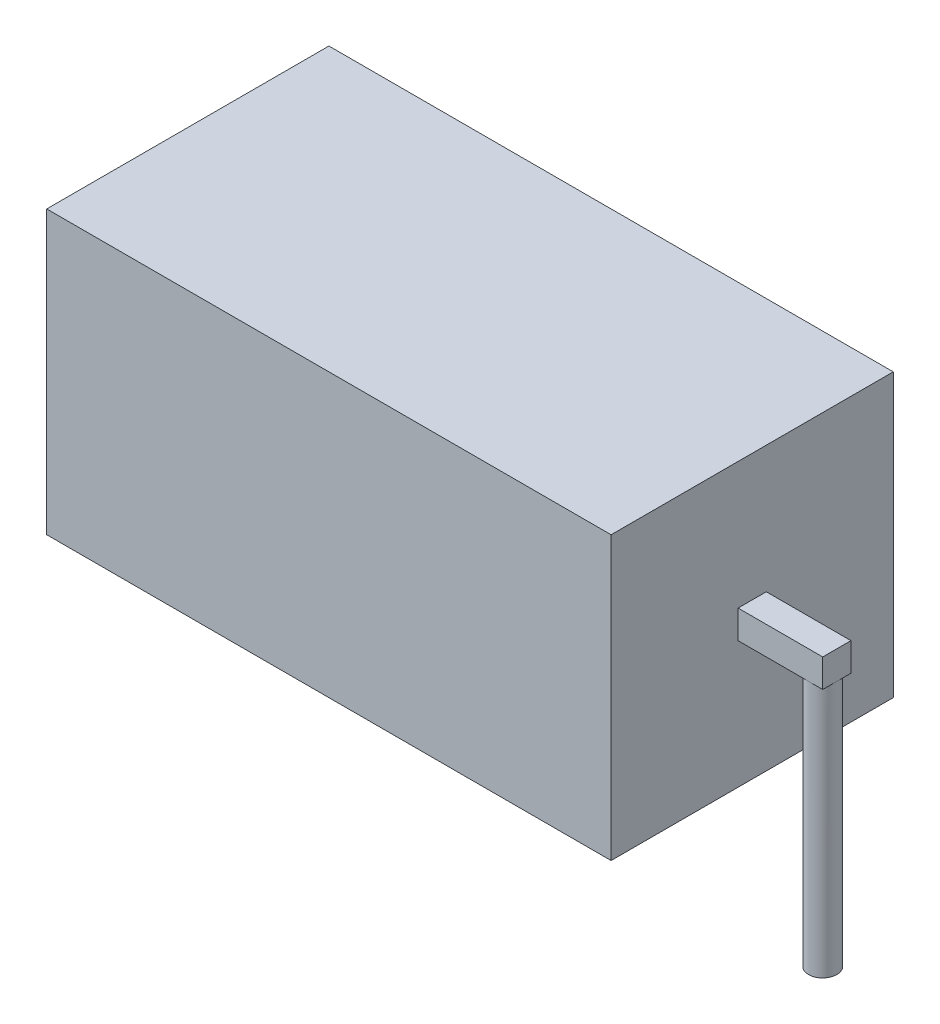
SolidWorks part; units mm, degrees
ref_plane "Спереди" through (0, 0, 0) normal (0, 0, 1) x (1, 0, 0)
ref_plane "Сверху" through (0, 0, 0) normal (0, 1, 0) x (1, 0, 0)
ref_plane "Справа" through (0, 0, 0) normal (1, 0, 0) x (0, 0, -1)
sketch "Эскиз1" plane through (0, 0, 0) normal (0, 0, 1) x (1, 0, 0)
  line L1 (0, 0) -> (20, 0)
  line L2 (0, 0) -> (0, 10)
  line L3 (0, 10) -> (20, 10)
  line L4 (20, 0) -> (20, 10)
  dimension "D1" = 10
  dimension "D2" = 20
extrude "Вытянуть1" add sketch "Эскиз1" along normal blind 10
sketch "Эскиз2" plane through (20, 0, 0) normal (1, 0, 0) x (0, 0, -1)
  line L0 (-10.8705, 5) -> (1.1033, 5) construction
  line L1 (-5, 10.8922) -> (-5, 4.5869) construction
  line L2 (-10, 10) -> (0, 10) construction
  line L3 (-10, 0) -> (0, 0) construction
  line L4 (-10, 0) -> (-10, 10) construction
  line L5 (0, 0) -> (0, 10) construction
  line L7 (-5.5, 4.5) -> (-4.5, 4.5)
  line L8 (-5.5, 4.5) -> (-5.5, 5.5)
  line L9 (-5.5, 5.5) -> (-4.5, 5.5)
  line L10 (-4.5, 4.5) -> (-4.5, 5.5)
  dimension "D1" = 1
extrude "Вытянуть2" add sketch "Эскиз2" along normal blind 3 and the other way blind 23
sketch "Эскиз3" plane through (0, 4.5, 0) normal (0, -1, 0) x (1, 0, 0)
  line L0 (-2.5, 5) -> (23.3087, 5) construction
  line L1 (0, 10) -> (20, 10) construction
  line L2 (0, 0) -> (20, 0) construction
  line L3 (10, 11.1302) -> (10, -1.0428) construction
  line L4 (0, 10) -> (0, 0) construction
  line L5 (20, 10) -> (20, 0) construction
  circle A0 centre (-2.5, 5) radius 0.5
  circle A1 centre (22.5, 5) radius 0.5
  dimension "D1" = 25
  dimension "D2" = 1
extrude "Вытянуть3" add sketch "Эскиз3" along normal blind 9
